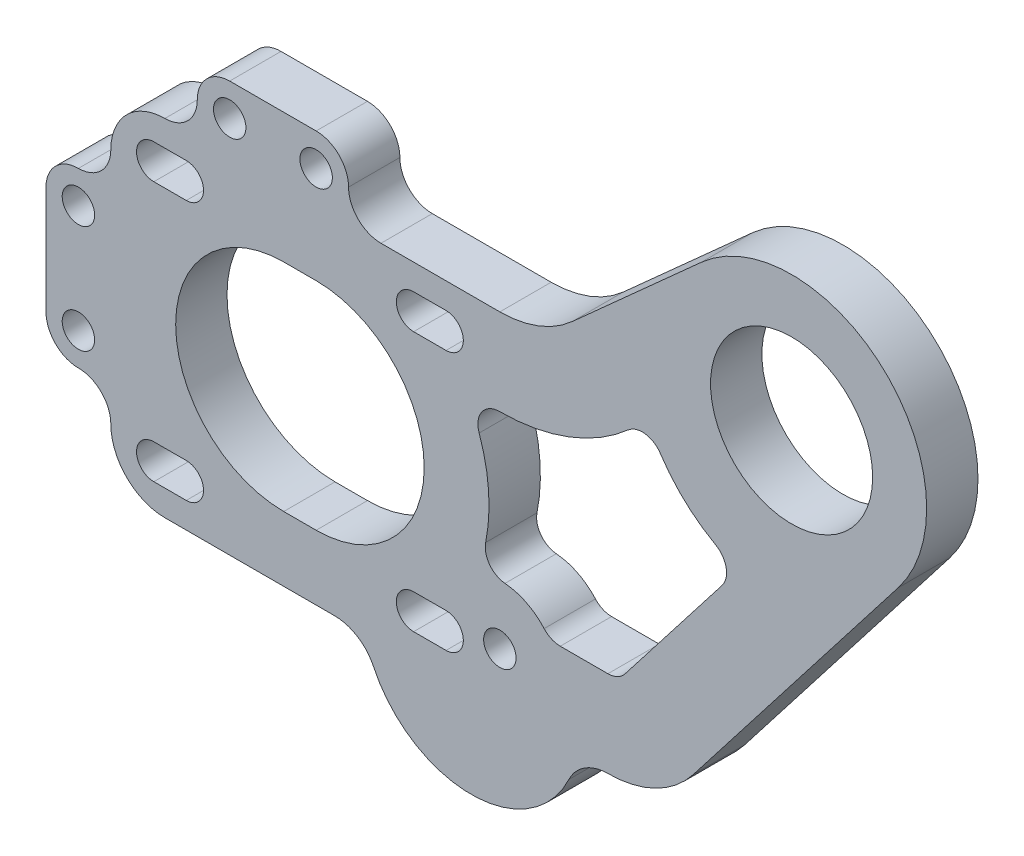
SolidWorks part; units mm, degrees
material "AISI Type A2 Tool Steel"
ref_plane "Front Plane" through (0, 0, 0) normal (0, 0, 1) x (1, 0, 0)
ref_plane "Top Plane" through (0, 0, 0) normal (0, 1, 0) x (1, 0, 0)
ref_plane "Right Plane" through (0, 0, 0) normal (1, 0, 0) x (0, 0, -1)
ref_axis "X" through (-88.99, 0, 0) along (1, 0, 0)
ref_axis "Y" through (0, 55, 0) along (0, -1, 0)
ref_axis "Z" through (0, 0, -88.99) along (0, 0, 1)
sketch "Sketch1" plane through (0, 0, 0) normal (0, 0, 1) x (1, 0, 0)
  line L0 (0, 0) -> (47, 0) construction
  line L1 (47, 0) -> (47, 20) construction
  line L2 (-16, 11) -> (-16, -11)
  line L3 (-11, -16) -> (30, -16)
  line L4 (37.9021, -12.1283) -> (56.8777, 12.3396)
  line L5 (-11, 16) -> (20, 16)
  line L6 (26.6796, 18.558) -> (38.6506, 29.3025)
  line L7 (0, 0) -> (47, 0) construction
  line L8 (47, 0) -> (47, 20) construction
  line L9 (20, 16) -> (20, 0) construction
  line L10 (30, -16) -> (30, 0) construction
  line L11 (0, 10) -> (3, 10)
  line L12 (3, -10) -> (0, -10)
  line L13 (-22, 5) -> (-22, -5)
  line L14 (-5, 22) -> (3, 22)
  line L15 (-19, 5) -> (-19, 8) construction
  line L16 (-19, 5) -> (-16, 5) construction
  line L17 (-8, 19) -> (-5, 19) construction
  line L18 (-5, 19) -> (-5, 16) construction
  line L19 (31.5804, -7.2257) -> (40.561, 4.3543)
  line L21 (31.8566, 12.4549) -> (32.0232, 12.6044)
  line L22 (20, 8) -> (19.9706, 8)
  line L23 (25.5902, -8) -> (30, -8)
  circle A0 centre (0, 0) radius 10
  circle A1 centre (47, 20) radius 7.5
  circle A2 centre (47, 20) radius 12.5
  circle A3 centre (0, 0) radius 16 construction
  arc A4 (-16, -11) -> (-11, -16) centre (-11, -11) ccw
  arc A5 (30, -16) -> (37.9021, -12.1283) centre (30, -6) ccw
  arc A6 (-16, 11) -> (-11, 16) centre (-11, 11) cw
  arc A7 (20, 16) -> (26.6796, 18.558) centre (20, 26) ccw
  arc A8 (3, 10) -> (3, -10) centre (3, 0) cw
  arc A9 (-16, 11) -> (-19, 8) centre (-19, 11) cw
  arc A10 (-19, 8) -> (-22, 5) centre (-19, 5) ccw
  arc A11 (-22, -5) -> (-19, -8) centre (-19, -5) ccw
  arc A12 (-19, -8) -> (-16, -11) centre (-19, -11) cw
  arc A13 (-11, 16) -> (-8, 19) centre (-11, 19) ccw
  arc A14 (-8, 19) -> (-5, 22) centre (-5, 19) cw
  arc A15 (3, 22) -> (6, 19) centre (3, 19) cw
  arc A16 (6, 19) -> (9, 16) centre (9, 19) ccw
  circle A17 centre (20, -11) radius 1.5
  circle A18 centre (-5, 19) radius 1.5
  circle A19 centre (3, 19) radius 1.5
  circle A20 centre (-19, -5) radius 1.5
  circle A21 centre (-19, 5) radius 1.5
  arc A22 (40.561, 4.3543) -> (39.9526, 7.3278) centre (38.9805, 5.5799) ccw
  arc A23 (39.9526, 7.3278) -> (34.8662, 12.0615) centre (47, 20) cw
  arc A24 (34.8662, 12.0615) -> (31.8566, 12.4549) centre (33.1926, 10.9665) ccw
  arc A26 (19.9706, 8) -> (18.0849, 5.3333) centre (19.9706, 6) ccw
  arc A27 (18.0849, 5.3333) -> (18.6896, -3.1363) centre (3, 0) cw
  arc A29 (30, -8) -> (31.5804, -7.2257) centre (30, -6) ccw
  arc A30 (32.0232, 12.6044) -> (20, 8) centre (20, 26) cw
  arc A31 (18.6896, -3.1363) -> (20.4773, -5.5207) centre (20.6508, -3.5283) ccw
  arc A32 (20.4773, -5.5207) -> (24.0995, -7.3333) centre (20, -11) cw
  arc A33 (24.0995, -7.3333) -> (25.5902, -8) centre (25.5902, -6) ccw
  arc A34 (30, -16) -> (26.386, -18.2857) centre (30, -20) ccw
  arc A35 (26.386, -18.2857) -> (8.3158, -18.2857) centre (17.3509, -14) cw
  arc A36 (8.3158, -18.2857) -> (4.7018, -16) centre (4.7018, -20) ccw
  point P84 (26.9487, -18.2654)
  point P85 (16.1037, -19.4322)
  point P86 (23.295, -19.6362)
  point P87 (17.3509, -24)
  dimension "D1" = 20
  dimension "D2" = 32
  dimension "D3" = 5
  dimension "D4" = 5
  dimension "D5" = 15
  dimension "D8" = 10
  dimension "D6" = 3
  dimension "D10" = 5
  dimension "D11" = 3
  dimension "D12" = 3
  dimension "D13" = 10
  dimension "D16" = 2
  dimension "D17" = 8
  dimension "D18" = 2
  dimension "D19" = 8
  dimension "D20" = 6
  dimension "D21" = 4
  dimension "D22" = 10
  dimension "D23" = 4
  dimension "D24" = 8
  dimension "D7" = 20
  dimension "D9" = 30
  dimension "D14" = 8
  dimension "D15" = 10
extrude "Boss-Extrude1" add sketch "Sketch1" along normal mid plane 4.75 contours A7 L5 A6 L2 A4 L3 A5 L4 A2 L6 A0 | A2 A1 | A16 A15 L14 A14 A13 L5 A19 A18 | A11 A12 L2 A9 A10 L13 A21 A20 | A36 A35 A34 L3 region at (14.3716, 0.6822, 0) region at (-18.7801, 0, 0) region at (-1, 18.7424, 0) region at (17.3509, -19.2799, 0) region at (51.9492, 31.0924, 0)
sketch "Sketch2" plane through (0, 0, 0) normal (0, 0, 1) x (1, 0, 0)
  line L0 (-12.0208, 12.0208) -> (-9.0208, 12.0208) construction
  line L1 (-12.0208, 13.6208) -> (-9.0208, 13.6208)
  line L2 (-12.0208, 10.4208) -> (-9.0208, 10.4208)
  line L3 (12.0208, 12.0208) -> (15.0208, 12.0208) construction
  line L4 (12.0208, 13.6208) -> (15.0208, 13.6208)
  line L5 (12.0208, 10.4208) -> (15.0208, 10.4208)
  line L6 (-12.0208, -12.0208) -> (-9.0208, -12.0208) construction
  line L7 (-12.0208, -10.4208) -> (-9.0208, -10.4208)
  line L8 (-12.0208, -13.6208) -> (-9.0208, -13.6208)
  line L9 (12.0208, -12.0208) -> (15.0208, -12.0208) construction
  line L10 (12.0208, -10.4208) -> (15.0208, -10.4208)
  line L11 (12.0208, -13.6208) -> (15.0208, -13.6208)
  line L12 (-12.0208, 12.0208) -> (-12.0208, -12.0208) construction
  line L13 (-12.0208, -12.0208) -> (12.0208, -12.0208) construction
  line L14 (12.0208, -12.0208) -> (12.0208, 12.0208) construction
  line L15 (12.0208, 12.0208) -> (-12.0208, 12.0208) construction
  circle A0 centre (0, 0) radius 17 construction
  arc A1 (-12.0208, 13.6208) -> (-12.0208, 10.4208) centre (-12.0208, 12.0208) ccw
  arc A2 (-9.0208, 10.4208) -> (-9.0208, 13.6208) centre (-9.0208, 12.0208) ccw
  arc A3 (12.0208, 13.6208) -> (12.0208, 10.4208) centre (12.0208, 12.0208) ccw
  arc A4 (15.0208, 10.4208) -> (15.0208, 13.6208) centre (15.0208, 12.0208) ccw
  arc A5 (-12.0208, -10.4208) -> (-12.0208, -13.6208) centre (-12.0208, -12.0208) ccw
  arc A6 (-9.0208, -13.6208) -> (-9.0208, -10.4208) centre (-9.0208, -12.0208) ccw
  arc A7 (12.0208, -10.4208) -> (12.0208, -13.6208) centre (12.0208, -12.0208) ccw
  arc A8 (15.0208, -13.6208) -> (15.0208, -10.4208) centre (15.0208, -12.0208) ccw
  point P5 (-10.5208, 12.0208)
  point P12 (13.5208, 12.0208)
  point P17 (-10.5208, -12.0208)
  point P24 (13.5208, -12.0208)
  dimension "D1" = 34
  dimension "D2" = 1.6
  dimension "D3" = 3
extrude "Cut-Extrude1" cut sketch "Sketch2" against normal through all both and the other way through all
